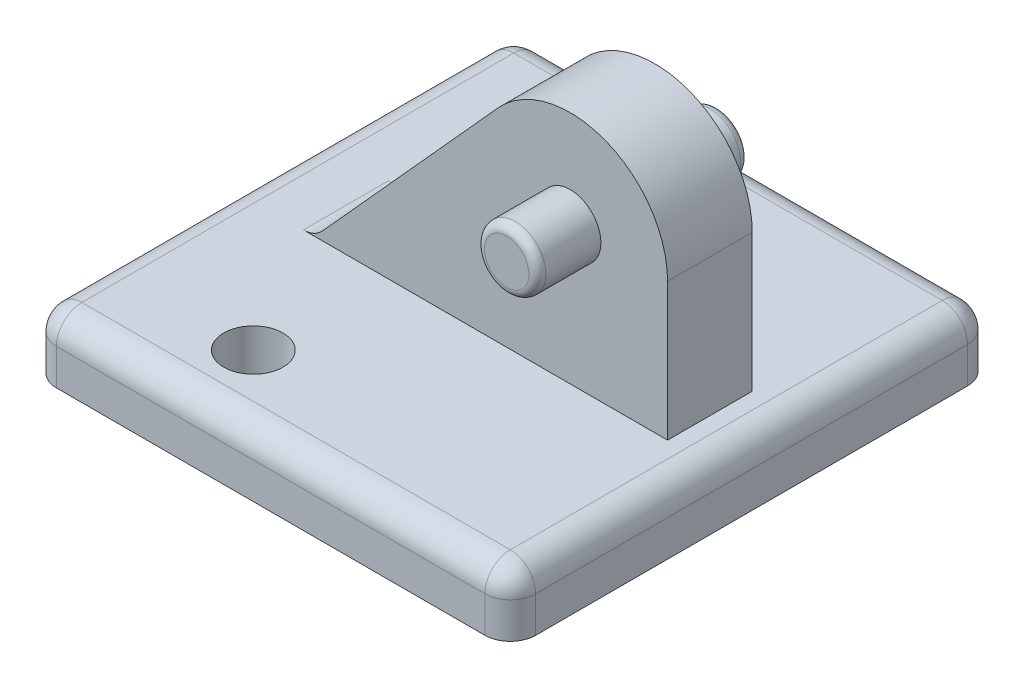
SolidWorks part; units mm, degrees
ref_plane "Front Plane" through (0, 0, 0) normal (0, 0, 1) x (1, 0, 0)
ref_plane "Top Plane" through (0, 0, 0) normal (0, 1, 0) x (1, 0, 0)
ref_plane "Right Plane" through (0, 0, 0) normal (1, 0, 0) x (0, 0, -1)
sketch "Sketch1" plane through (0, 0, 0) normal (0, 1, 0) x (1, 0, 0)
  line L0 (0, 0) -> (-2.6162, 5.1435) construction
  line L1 (-7.1882, 7.239) -> (7.1882, 7.239)
  line L2 (-7.1882, 7.239) -> (-7.1882, -7.239)
  line L3 (-7.1882, -7.239) -> (7.1882, -7.239)
  line L4 (7.1882, 7.239) -> (7.1882, -7.239)
  line L5 (-2.6162, -5.1435) -> (0, 0) construction
  circle A0 centre (-2.6162, 5.1435) radius 0.889
  circle A1 centre (-2.6162, -5.1435) radius 0.889
  point P4 (0, 7.239)
  point P5 (-7.1882, 0)
  dimension "D3" = 1.778
  dimension "D4" = 1.778
  dimension "D5" = 4.572
  dimension "D1" = 14.478
  dimension "D2" = 14.3764
  dimension "D6" = 2.0955
extrude "Boss-Extrude1" add sketch "Sketch1" along normal blind 1.8415
sketch "Sketch2" plane through (0, 0, 0) normal (0, 0, 1) x (1, 0, 0)
  line L0 (-7.1882, 1.8415) -> (7.1882, 1.8415) construction
  line L1 (-7.1882, 1.8415) -> (7.1882, 1.8415)
  line L5 (-4.6482, 1.8415) -> (0.8482, 7.9269)
  line L6 (5.9369, 5.969) -> (5.9369, 1.8415)
  circle A2 centre (3.0159, 5.969) radius 0.9207
  arc A3 (0.8482, 7.9269) -> (5.9369, 5.969) centre (3.0159, 5.969) cw
  dimension "D1" = 1.2513
  dimension "D4" = 1.8415
  dimension "D5" = 2.921
  dimension "D2" = 4.1275
  dimension "D3" = 2.54
extrude "Boss-Extrude2" add sketch "Sketch2" along normal mid plane 2.54 contours L1 A2 region at (1.8257, 4.65, 0)
extrude "Boss-Extrude3" add sketch "Sketch2<4>" along normal mid plane 6.35 contours A2 region at (3.0159, 5.969, 0)
sketch "Sketch2<4>" plane through (0, 0, 0) normal (0, 0, 1) x (1, 0, 0) same geometry as "Sketch2"
fillet "Fillet1" radius 0.762 9 edges at (7.1882, 0.9207, -7.239) (-7.1882, 0.9207, -7.239) (7.1882, 0.9207, 7.239) (-7.1882, 0.9207, 7.239) (7.1882, 1.8415, 0) (0, 1.8415, -7.239) (0, 1.8415, 7.239) (-7.1882, 1.8415, 0) (-4.6482, 1.8415, 0)
fillet "Fillet2" radius 0.254 2 edges at (3.9366, 5.969, -3.175) (3.9366, 5.969, 3.175)
